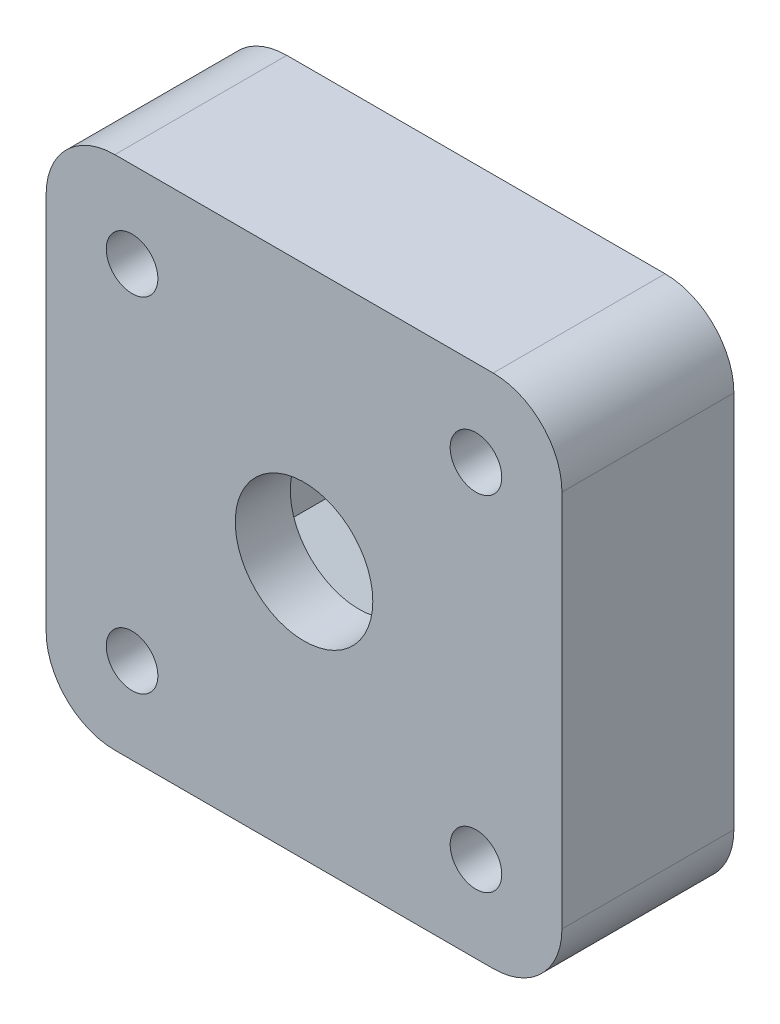
SolidWorks part; units mm, degrees
ref_plane "정면" through (0, 0, 0) normal (0, 0, 1) x (1, 0, 0)
ref_plane "윗면" through (0, 0, 0) normal (0, 1, 0) x (1, 0, 0)
ref_plane "우측면" through (0, 0, 0) normal (1, 0, 0) x (0, 0, -1)
sketch "스케치1" plane through (0, 0, 0) normal (0, 0, 1) x (1, 0, 0)
  line L0 (0, 10) -> (0, -10) construction
  line L1 (6, 3.4641) -> (0, 6.9282)
  line L2 (0, 6.9282) -> (-6, 3.4641)
  line L3 (-6, 3.4641) -> (-6, -3.4641)
  line L4 (-6, -3.4641) -> (0, -6.9282)
  line L5 (0, -6.9282) -> (6, -3.4641)
  line L6 (6, -3.4641) -> (6, 3.4641)
  line L7 (-15, -15) -> (15, -15)
  line L8 (-15, -15) -> (-15, 15)
  line L9 (-15, 15) -> (15, 15)
  line L10 (15, -15) -> (15, 15)
  line L11 (-15, -15) -> (15, 15) construction
  line L12 (-15, 15) -> (15, -15) construction
  line L13 (-10, -10) -> (10, -10) construction
  line L14 (-10, -10) -> (-10, 10) construction
  line L15 (-10, 10) -> (10, 10) construction
  line L16 (10, -10) -> (10, 10) construction
  line L17 (-10, -10) -> (10, 10) construction
  line L18 (-10, 10) -> (10, -10) construction
  line L19 (-10, 0) -> (10, 0) construction
  circle A0 centre (0, 0) radius 6 construction
  circle A1 centre (-10, 10) radius 1.5
  circle A2 centre (10, 10) radius 1.5
  circle A3 centre (10, -10) radius 1.5
  circle A4 centre (-10, -10) radius 1.5
  circle A5 centre (0, 0) radius 4
  dimension "D4" = 3
  dimension "D5" = 8
  dimension "D1" = 12
  dimension "D2" = 30
  dimension "D3" = 20
extrude "보스-돌출1" add sketch "스케치1" along normal blind 10 contours L7 L10 L9 L8 A2 A1 L6 L5 L4 L3 L2 L1 A3 A4 | L5 L6 L1 L2 L3 L4 region at (5.8167, 0, 0) region at (-14.5757, 0, 0)
extrude "컷-돌출1" cut sketch "스케치1<3>" along normal blind 6.8 contours L2 L3 L4 L5 L6 L1
sketch "스케치1<3>" plane through (0, 0, 0) normal (0, 0, 1) x (1, 0, 0) same geometry as "스케치1"
fillet "필렛1" radius 4 4 edges at (-15, 15, 5) (-15, -15, 5) (15, -15, 5) (15, 15, 5)
